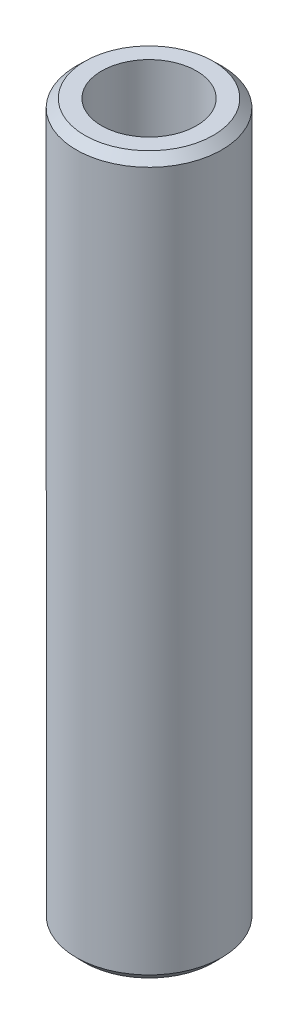
SolidWorks part; units mm, degrees
ref_plane "Front Plane" through (0, 0, 0) normal (0, 0, 1) x (1, 0, 0)
ref_plane "Top Plane" through (0, 0, 0) normal (0, 1, 0) x (1, 0, 0)
ref_plane "Right Plane" through (0, 0, 0) normal (1, 0, 0) x (0, 0, -1)
sketch "Sketch1" plane through (0, 0, 0) normal (0, 1, 0) x (1, 0, 0)
  circle A0 centre (0, 0) radius 35
  dimension "SHAFT_OD" = 70
extrude "Boss-Extrude1" add sketch "Sketch1" along normal blind 344.5662
sketch "Sketch2" plane through (0, 0, 0) normal (0, 1, 0) x (1, 0, 0)
  circle A0 centre (0, 0) radius 22.8428
  dimension "BORE_D" = 45.6855
extrude "Cut-Extrude1" cut sketch "Sketch2" along normal through all
chamfer "Chamfer1" distance 3.9894 angle 45.833 2 edges at (0, 344.5662, 35) (0, 0, 35) first distance on face at (0, 344.5662, 35) first distance on face at (0, 0, 22.8428)
